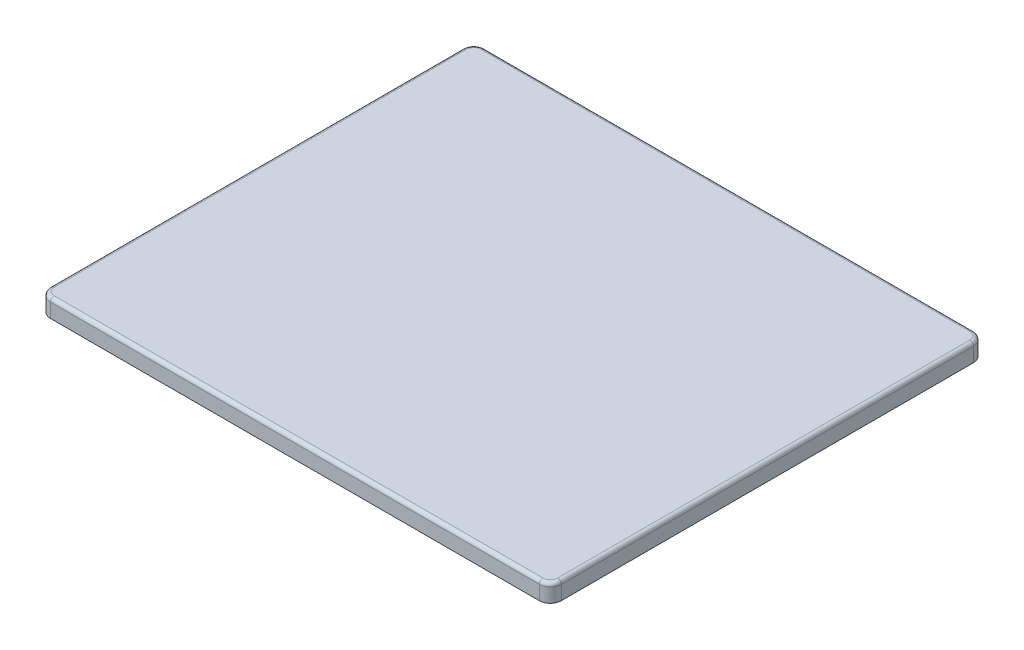
SolidWorks part; units mm, degrees
material "ABS"
ref_plane "Front Plane" through (0, 0, 0) normal (0, 0, 1) x (1, 0, 0)
ref_plane "Top Plane" through (0, 0, 0) normal (0, 1, 0) x (1, 0, 0)
ref_plane "Right Plane" through (0, 0, 0) normal (1, 0, 0) x (0, 0, -1)
sketch "Sketch1" plane through (0, 0, 0) normal (0, 1, 0) x (1, 0, 0)
  line L1 (-70, -59.5) -> (70, -59.5)
  line L2 (-70, -59.5) -> (-70, 59.5)
  line L3 (-70, 59.5) -> (70, 59.5)
  line L4 (70, -59.5) -> (70, 59.5)
  line L5 (-70, -59.5) -> (70, 59.5) construction
  line L6 (-70, 59.5) -> (70, -59.5) construction
  point P0 (0, 0)
  dimension "D1" = 119
  dimension "D2" = 140
extrude "Boss-Extrude1" add sketch "Sketch1" along normal blind 5
fillet "Fillet1" radius 3 4 edges at (70, 2.5, 59.5) (-70, 2.5, -59.5) (70, 2.5, -59.5) (-70, 2.5, 59.5)
shell "Shell1" thickness 3 removed face at (0, 0, 0)
fillet "Fillet2" radius 3 4 edges at (67, 1, -56.5) (-67, 1, -56.5) (67, 1, 56.5) (-67, 1, 56.5)
sketch "Sketch2" plane through (0, 0, 0) normal (0, -1, 0) x (1, 0, 0)
  line L22 (67, 53.5) -> (67, -53.5) construction
  line L23 (64, -56.5) -> (-64, -56.5) construction
  line L24 (-67, -53.5) -> (-67, 53.5) construction
  line L25 (-64, 56.5) -> (64, 56.5) construction
  line L26 (68.5, -53.5) -> (68.5, 53.5)
  line L27 (-64, -58) -> (64, -58)
  line L28 (-68.5, 53.5) -> (-68.5, -53.5)
  line L29 (64, 58) -> (-64, 58)
  line L30 (68.5, -53.5) -> (68.5, 53.5)
  line L31 (-64, -58) -> (64, -58)
  line L32 (-68.5, 53.5) -> (-68.5, -53.5)
  line L33 (64, 58) -> (-64, 58)
  line L34 (67, 53.5) -> (67, -53.5)
  line L35 (64, -56.5) -> (-64, -56.5)
  line L36 (-67, -53.5) -> (-67, 53.5)
  line L37 (-64, 56.5) -> (64, 56.5)
  arc A14 (67, 53.5) -> (64, 56.5) centre (64, 53.5) ccw construction
  arc A15 (64, -56.5) -> (67, -53.5) centre (64, -53.5) ccw construction
  arc A16 (-67, -53.5) -> (-64, -56.5) centre (-64, -53.5) ccw construction
  arc A17 (-64, 56.5) -> (-67, 53.5) centre (-64, 53.5) ccw construction
  arc A18 (68.5, 53.5) -> (64, 58) centre (64, 53.5) ccw
  arc A19 (64, -58) -> (68.5, -53.5) centre (64, -53.5) ccw
  arc A20 (-68.5, -53.5) -> (-64, -58) centre (-64, -53.5) ccw
  arc A21 (-64, 58) -> (-68.5, 53.5) centre (-64, 53.5) ccw
  arc A22 (68.5, 53.5) -> (64, 58) centre (64, 53.5) ccw
  arc A23 (64, -58) -> (68.5, -53.5) centre (64, -53.5) ccw
  arc A24 (-68.5, -53.5) -> (-64, -58) centre (-64, -53.5) ccw
  arc A25 (-64, 58) -> (-68.5, 53.5) centre (-64, 53.5) ccw
  arc A26 (67, 53.5) -> (64, 56.5) centre (64, 53.5) ccw
  arc A27 (64, -56.5) -> (67, -53.5) centre (64, -53.5) ccw
  arc A28 (-67, -53.5) -> (-64, -56.5) centre (-64, -53.5) ccw
  arc A29 (-64, 56.5) -> (-67, 53.5) centre (-64, 53.5) ccw
  dimension "D1" = 1.5
extrude "Cut-Extrude1" cut sketch "Sketch2" against normal blind 1
sketch "Sketch3" plane through (0, 0, 0) normal (0, -1, 0) x (1, 0, 0)
  line L0 (-64, -58) -> (64, -58) construction
  line L1 (68.5, -53.5) -> (68.5, 53.5) construction
  line L2 (64, 58) -> (-64, 58) construction
  line L3 (-68.5, 53.5) -> (-68.5, -53.5) construction
  line L4 (70, -56.5) -> (70, 56.5)
  line L5 (67, 59.5) -> (-67, 59.5)
  line L6 (-70, 56.5) -> (-70, -56.5)
  line L7 (-67, -59.5) -> (67, -59.5)
  line L8 (70, -56.5) -> (70, 56.5)
  line L9 (67, 59.5) -> (-67, 59.5)
  line L10 (-70, 56.5) -> (-70, -56.5)
  line L11 (-67, -59.5) -> (67, -59.5)
  line L12 (-64, -58) -> (64, -58)
  line L13 (68.5, -53.5) -> (68.5, 53.5)
  line L14 (64, 58) -> (-64, 58)
  line L15 (-68.5, 53.5) -> (-68.5, -53.5)
  arc A0 (-68.5, -53.5) -> (-64, -58) centre (-64, -53.5) ccw construction
  arc A1 (64, -58) -> (68.5, -53.5) centre (64, -53.5) ccw construction
  arc A2 (68.5, 53.5) -> (64, 58) centre (64, 53.5) ccw construction
  arc A3 (-64, 58) -> (-68.5, 53.5) centre (-64, 53.5) ccw construction
  arc A4 (70, 56.5) -> (67, 59.5) centre (67, 56.5) ccw
  arc A5 (-67, 59.5) -> (-70, 56.5) centre (-67, 56.5) ccw
  arc A6 (-70, -56.5) -> (-67, -59.5) centre (-67, -56.5) ccw
  arc A7 (67, -59.5) -> (70, -56.5) centre (67, -56.5) ccw
  arc A8 (70, 56.5) -> (67, 59.5) centre (67, 56.5) ccw
  arc A9 (-67, 59.5) -> (-70, 56.5) centre (-67, 56.5) ccw
  arc A10 (-70, -56.5) -> (-67, -59.5) centre (-67, -56.5) ccw
  arc A11 (67, -59.5) -> (70, -56.5) centre (67, -56.5) ccw
  arc A12 (-68.5, -53.5) -> (-64, -58) centre (-64, -53.5) ccw
  arc A13 (64, -58) -> (68.5, -53.5) centre (64, -53.5) ccw
  arc A14 (68.5, 53.5) -> (64, 58) centre (64, 53.5) ccw
  arc A15 (-64, 58) -> (-68.5, 53.5) centre (-64, 53.5) ccw
  dimension "D1" = 0
extrude "Cut-Extrude2" cut sketch "Sketch3" against normal blind 0.1
fillet "Fillet3" radius 1 8 edges at (-69.1213, 5, 58.6213) (-70, 5, 0) (-69.1213, 5, -58.6213) (0, 5, -59.5) (69.1213, 5, -58.6213) (70, 5, 0) (69.1213, 5, 58.6213) (0, 5, 59.5)
fillet "Fillet5" radius 0.5 16 edges at (68.5, 0.1, 0) (67.182, 0.1, -56.682) (0, 0.1, -58) (-67.182, 0.1, -56.682) (-68.5, 0.1, 0) (-67.182, 0.1, 56.682) (0, 0.1, 58) (67.182, 0.1, 56.682) (0, 1, 56.5) (66.1213, 1, 55.6213) (67, 1, 0) (66.1213, 1, -55.6213) (0, 1, -56.5) (-66.1213, 1, -55.6213) (-67, 1, 0) (-66.1213, 1, 55.6213)
